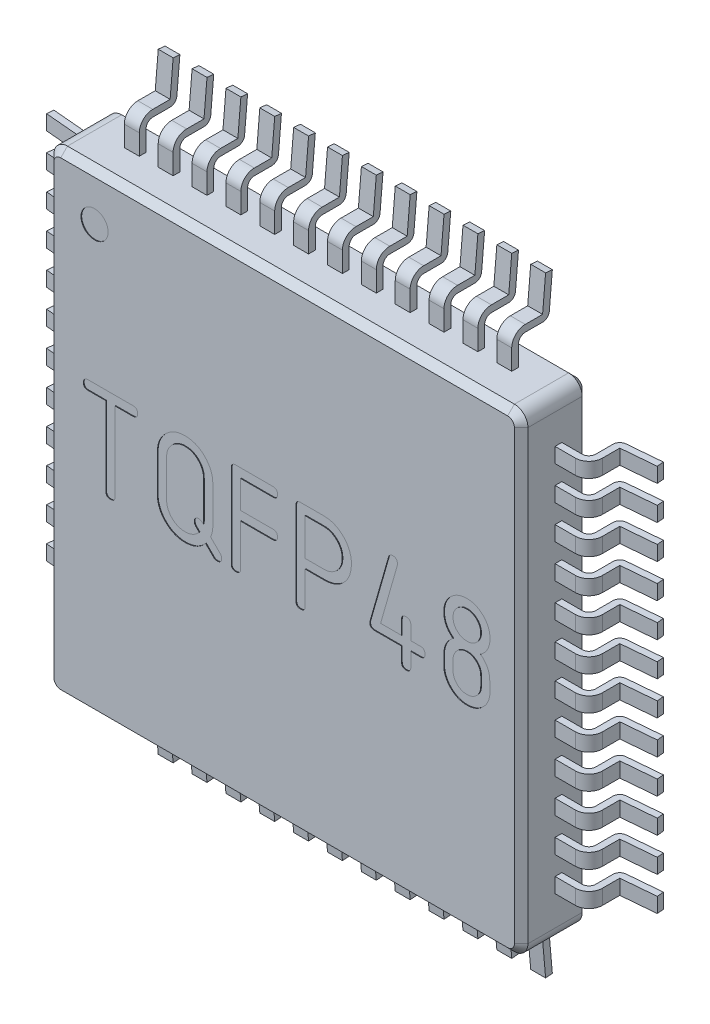
SolidWorks part; units mm, degrees
ref_plane "Спереди" through (0, 0, 0) normal (0, 0, 1) x (1, 0, 0)
ref_plane "Сверху" through (0, 0, 0) normal (0, 1, 0) x (1, 0, 0)
ref_plane "Справа" through (0, 0, 0) normal (1, 0, 0) x (0, 0, -1)
ref_axis "Ось1" through (0, 0, -0.055) along (0, 0, 1)
sketch "Эскиз1" plane through (0, 0, 0) normal (0, 0, 1) x (1, 0, 0)
  line L0 (0, 0) -> (-4.5, 0) construction
  line L1 (-3.5, -3.5) -> (3.5, -3.5)
  line L2 (-3.5, -3.5) -> (-3.5, 3.5)
  line L3 (-3.5, 3.5) -> (3.5, 3.5)
  line L4 (3.5, -3.5) -> (3.5, 3.5)
  line L5 (-3.5, -3.5) -> (3.5, 3.5) construction
  line L6 (-3.5, 3.5) -> (3.5, -3.5) construction
  line L7 (-4.5, -4.5) -> (4.5, -4.5)
  line L8 (-4.5, -4.5) -> (-4.5, 4.5)
  line L9 (-4.5, 4.5) -> (4.5, 4.5)
  line L10 (4.5, -4.5) -> (4.5, 4.5)
  line L11 (-4.5, -4.5) -> (4.5, 4.5) construction
  line L12 (-4.5, 4.5) -> (4.5, -4.5) construction
  point P0 (0, 0)
  point P6 (0, 0)
  point P13 (-3.5, 0.75)
  point P14 (-3.5, 1.25)
  point P15 (-3.5, 1.75)
  point P16 (-3.5, 2.25)
  point P17 (-3.5, -2.25)
  point P18 (-3.5, -1.75)
  point P19 (-3.5, -1.25)
  point P20 (-3.5, -0.75)
  point P21 (-3.5, 0.25)
  point P22 (-3.5, 2.75)
  point P23 (-3.5, -2.75)
  point P24 (-3.5, -0.25)
ref_plane "Плоскость1" through (0, 0, 0.1) normal (0, 0, 1) x (1, 0, 0)
ref_plane "Плоскость2" through (0, 2.75, 0) normal (0, 1, 0) x (-1, 0, 0)
sketch "Эскиз2" plane through (0, 0, 0.1) normal (0, 0, 1) x (1, 0, 0)
  line L0 (-3.5, 3.5) -> (3.5, 3.5) construction
  line L1 (-3.5, -3.5) -> (-3.5, 3.5) construction
  line L2 (-3.5, -3.5) -> (3.5, -3.5) construction
  line L3 (3.5, -3.5) -> (3.5, 3.5) construction
  line L4 (-3.3, 3.5) -> (3.3, 3.5)
  line L5 (-3.5, -3.3) -> (-3.5, 3.3)
  line L6 (-3.3, -3.5) -> (3.3, -3.5)
  line L7 (3.5, -3.3) -> (3.5, 3.3)
  arc A0 (-3.5, -3.3) -> (-3.3, -3.5) centre (-3.3, -3.3) ccw
  arc A1 (3.3, -3.5) -> (3.5, -3.3) centre (3.3, -3.3) ccw
  arc A2 (3.3, 3.5) -> (3.5, 3.3) centre (3.3, 3.3) cw
  arc A3 (-3.3, 3.5) -> (-3.5, 3.3) centre (-3.3, 3.3) ccw
  dimension "D1" = 0.2
extrude "Бобышка-Вытянуть1" add sketch "Эскиз2" along normal blind 1
chamfer "Фаска1" distance 0.1 angle 45 16 edges at (0, 3.5, 0.1) (-3.4414, 3.4414, 0.1) (3.4414, 3.4414, 0.1) (-3.5, 0, 0.1) (3.5, 0, 0.1) (-3.4414, -3.4414, 0.1) (3.4414, -3.4414, 0.1) (0, -3.5, 0.1) (0, 3.5, 1.1) (-3.4414, 3.4414, 1.1) (3.4414, 3.4414, 1.1) (-3.5, 0, 1.1) (3.5, 0, 1.1) (-3.4414, -3.4414, 1.1) (3.4414, -3.4414, 1.1) (0, -3.5, 1.1)
sketch "Эскиз3" plane through (0, 2.75, 0) normal (0, 1, 0) x (-1, 0, 0)
  line L0 (3.5, 0.5) -> (3.8, 0.5)
  line L1 (3.9, 0.4) -> (3.9, 0.1441)
  line L2 (3.9913, 0.0445) -> (4.5, 0)
  line L3 (4.9596, 0) -> (-4.9596, 0) construction
  line L4 (3.5, 0.6) -> (3.8, 0.6)
  line L5 (4, 0.4) -> (4, 0.1441)
  line L6 (4, 0.1441) -> (4.5087, 0.0996)
  line L7 (3.5, 0.5) -> (3.5, 0.6)
  line L8 (4.5, 0) -> (4.5087, 0.0996)
  arc A0 (3.9, 0.1441) -> (3.9913, 0.0445) centre (4, 0.1441) ccw
  arc A1 (3.8, 0.5) -> (3.9, 0.4) centre (3.8, 0.4) cw
  arc A2 (3.8, 0.6) -> (4, 0.4) centre (3.8, 0.4) cw
  arc A3 (4, 0.1441) -> (4, 0.1441) centre (4, 0.1441) ccw
  dimension "D1" = 0.1
  dimension "D2" = 0.6
  dimension "D3" = 5
  dimension "D4" = 0.5
  dimension "D5" = 0.1
extrude "Бобышка-Вытянуть2" add sketch "Эскиз3" along normal blind 0.11 and the other way blind 0.11
pattern_linear "Линейный массив1" count 12 spacing 0.5 along (0, -1, 0) of "Бобышка-Вытянуть2"
pattern_circular "Круговой массив1" count 4 over 360 about axis through (0, 0, -0.055) along (0, 0, 1) of "Бобышка-Вытянуть2", "Линейный массив1"
sketch "Эскиз4" plane through (0, 0, 1.1) normal (0, 0, 1) x (1, 0, 0)
  circle A0 centre (-2.8, 2.8) radius 0.2
  text T0 "TQFP48" font "ГОСТ тип А" height in points 6
  dimension "D1" = 0.4
  dimension "D2" = 3.1
  dimension "D3" = 0.6
extrude "Вырез-Вытянуть1" cut sketch "Эскиз4" against normal blind 0.01
